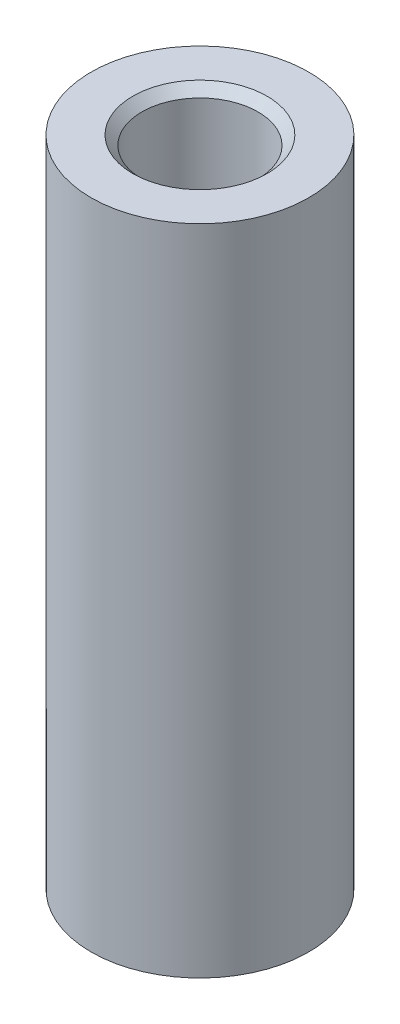
SolidWorks part; units mm, degrees
material "6061-T6 (SS)"
ref_plane "Front Plane" through (0, 0, 0) normal (0, 0, 1) x (1, 0, 0)
ref_plane "Top Plane" through (0, 0, 0) normal (0, 1, 0) x (1, 0, 0)
ref_plane "Right Plane" through (0, 0, 0) normal (1, 0, 0) x (0, 0, -1)
sketch "Sketch1" plane through (0, 0, 0) normal (0, 1, 0) x (1, 0, 0)
  circle A0 centre (0, 0) radius 3
  dimension "D1" = 6
extrude "Boss-Extrude1" add sketch "Sketch1" along normal blind 18
hole_wizard "M3 Clearance Hole1" positions "Sketch2" profile "Sketch4" hole size "M3" standard "ANSI Metric" end condition through all
sketch "Sketch2" plane through (0, 18, 0) normal (0, 1, 0) x (1, 0, 0)
  point P0 (0, 0)
sketch "Sketch4" plane through (0, 18, 0) normal (1, 0, 0) x (0, 0, 1)
  line L0 (0, 0) -> (0, 18)
  line L1 (0, 18) -> (1.6, 18)
  line L2 (1.6, 18) -> (1.6, 0)
  line L5 (1.6, 0) -> (0, 0)
  line L11 (0, -6.35) -> (0, 107.95) construction
  dimension "Thru Hole Dia." = 3.2
  dimension "Thru Hole Depth" = 18
chamfer "Chamfer1" distance 0.25 angle 45 2 edges at (0, 18, 1.6) (0, 0, 1.6)
